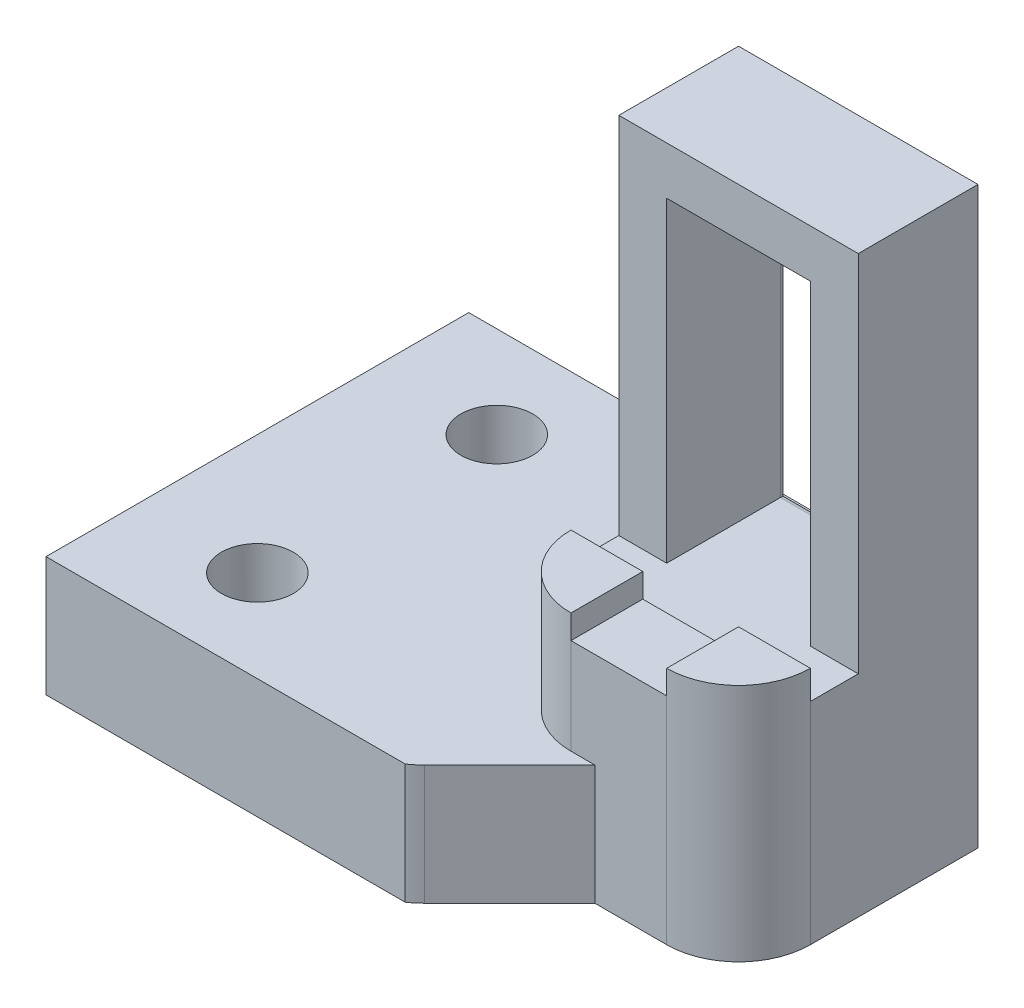
SolidWorks part; units mm, degrees
other "标注1"
sketch "草图8" plane through (-30, 24, -10.05) normal (-0.0333, 0.0376, -0.9987) x (-0.9561, 0.2897, 0.0428)
sketch "草图10" plane through (-30, 24, -10.05) normal (-0.0333, 0.0376, -0.9987) x (-0.9561, 0.2897, 0.0428)
sketch "草图23" plane through (-30, 24, -10) normal (-0.0333, 0.0376, -0.9987) x (-0.9561, 0.2897, 0.0428)
sketch "草图26" plane through (-30, 24, -10) normal (-0.0333, 0.0376, -0.9987) x (-0.9561, 0.2897, 0.0428)
sketch "草图30" plane through (-30, 24, -10) normal (-0.0333, 0.0376, -0.9987) x (-0.9561, 0.2897, 0.0428)
sketch "草图33" plane through (-30, 24, -10) normal (-0.0333, 0.0376, -0.9987) x (-0.9561, 0.2897, 0.0428)
sketch "草图41" plane through (-30, 24, -30) normal (-0.0333, 0.0376, -0.9987) x (-0.9561, 0.2897, 0.0428)
sketch "草图50" plane through (-62, 24, -30) normal (-0.0333, 0.0376, -0.9987) x (-0.9561, 0.2897, 0.0428)
sketch "草图56" plane through (-45, 24, -13.7305) normal (-0.0333, 0.0376, -0.9987) x (-0.9561, 0.2897, 0.0428)
other "标注2"
sketch "草图16" plane through (0, 24, 0) normal (0.8795, 0.3038, 0.3663) x (0.4513, -0.2881, -0.8446)
sketch "草图24" plane through (0, 24, 0) normal (0.8795, 0.3038, 0.3663) x (0.4513, -0.2881, -0.8446)
sketch "草图27" plane through (0, 24, 0) normal (0.8795, 0.3038, 0.3663) x (0.4513, -0.2881, -0.8446)
sketch "草图31" plane through (0, 24, 0) normal (0.8795, 0.3038, 0.3663) x (0.4513, -0.2881, -0.8446)
sketch "草图34" plane through (0, 24, 0) normal (0.8795, 0.3038, 0.3663) x (0.4513, -0.2881, -0.8446)
sketch "草图42" plane through (-10, 24, 10) normal (0.8795, 0.3038, 0.3663) x (0.4513, -0.2881, -0.8446)
sketch "草图51" plane through (-10, 24, 10) normal (0.8795, 0.3038, 0.3663) x (0.4513, -0.2881, -0.8446)
sketch "草图57" plane through (-10, 24, 3.9243) normal (0.8795, 0.3038, 0.3663) x (0.4513, -0.2881, -0.8446)
other "标注3"
sketch "草图17" plane through (0, 24, 0) normal (0.8795, 0.3038, 0.3663) x (0.4513, -0.2881, -0.8446)
sketch "草图25" plane through (0, 24, 0) normal (0.8795, 0.3038, 0.3663) x (0.4513, -0.2881, -0.8446)
sketch "草图28" plane through (0, 24, 0) normal (0.8795, 0.3038, 0.3663) x (0.4513, -0.2881, -0.8446)
sketch "草图32" plane through (0, 24, 0) normal (0.8795, 0.3038, 0.3663) x (0.4513, -0.2881, -0.8446)
sketch "草图35" plane through (0, 24, 0) normal (0.8795, 0.3038, 0.3663) x (0.4513, -0.2881, -0.8446)
sketch "草图43" plane through (-10, 24, 10) normal (0.8795, 0.3038, 0.3663) x (0.4513, -0.2881, -0.8446)
sketch "草图52" plane through (-10, 24, 10) normal (0.8795, 0.3038, 0.3663) x (0.4513, -0.2881, -0.8446)
sketch "草图58" plane through (-10, 24, 3.9243) normal (0.8795, 0.3038, 0.3663) x (0.4513, -0.2881, -0.8446)
other "标注4"
sketch "草图37" plane through (-30, 24, -10) normal (-0.8775, 0.4051, -0.2566) x (-0.3121, -0.0762, 0.947)
sketch "草图44" plane through (-30, 24, -30) normal (-0.8775, 0.4051, -0.2566) x (-0.3121, -0.0762, 0.947)
sketch "草图53" plane through (-62, 24, -30) normal (-0.8775, 0.4051, -0.2566) x (-0.3121, -0.0762, 0.947)
sketch "草图59" plane through (-45, 24, -13.7305) normal (-0.8775, 0.4051, -0.2566) x (-0.3121, -0.0762, 0.947)
ref_plane "前视基准面" through (0, 0, 0) normal (0, 0, 1) x (1, 0, 0)
ref_plane "上视基准面" through (0, 0, 0) normal (0, 1, 0) x (1, 0, 0)
ref_plane "右视基准面" through (0, 0, 0) normal (1, 0, 0) x (0, 0, -1)
other "Configuration Table"
sketch "草图1" plane through (0, 0, 0) normal (0, 1, 0) x (1, 0, 0)
  line L0 (-20, 0) -> (-20, -5)
  line L2 (0, 0) -> (0, 10)
  line L3 (0, 10) -> (-30, 10)
  line L4 (-30, 0) -> (-30, 10)
  line L5 (-20, -5) -> (-10, -5)
  line L6 (-10, -5) -> (-10, 0)
  line L7 (-30, 0) -> (-20, 0)
  line L8 (-10, 0) -> (0, 0)
  dimension "D1" = 10
  dimension "D2" = 30
  dimension "D3" = 10
  dimension "D4" = 10
  dimension "D5" = 5
  dimension "D6" = 5
extrude "凸台-拉伸1" add sketch "草图1" along normal blind 4
sketch "草图2" plane through (0, 4, 0) normal (0, 1, 0) x (1, 0, 0)
  line L7 (0, 10) -> (-30, 10) construction
  line L8 (-20, -5) -> (-10, -5)
  line L9 (-20, -5) -> (-20, 10)
  line L10 (-20, 10) -> (-10, 10)
  line L11 (-10, -5) -> (-10, 10)
extrude "凸台-拉伸2" add sketch "草图2" along normal blind 20
sketch "草图3" plane through (0, 4, 0) normal (0, 1, 0) x (1, 0, 0)
  line L2 (0, 10) -> (-10, 10) construction
  line L3 (0, 0) -> (0, 10) construction
  circle A1 centre (-5, 5) radius 1.45
  dimension "D3" = 5
  dimension "D4" = 5
  dimension "D6" = 2.9
extrude "切除-拉伸1" cut sketch "草图3" against normal blind 20
sketch "草图4" plane through (0, 0, -10) normal (0, 0, -1) x (-1, 0, 0)
  line L6 (10, 24) -> (10, 4) construction
  line L7 (12, 22) -> (18, 22)
  line L8 (12, 22) -> (12, 8.8)
  line L9 (12, 8.8) -> (18, 8.8)
  line L10 (18, 22) -> (18, 8.8)
  line L11 (10, 24) -> (20, 24) construction
  dimension "D1" = 6
  dimension "D2" = 13.2
  dimension "D3" = 2
  dimension "D4" = 2
extrude "切除-拉伸2" cut sketch "草图4" against normal blind 9.5
sketch "草图6" plane through (0, 0, -0.5) normal (0, 0, -1) x (-1, 0, 0)
  line L0 (15, 22) -> (15, 20.68) construction
  line L1 (18, 22) -> (12, 22) construction
  line L2 (15, 20.68) -> (15, 15.6) construction
  line L3 (15, 15.6) -> (15, 10.52) construction
  circle A0 centre (15, 20.68) radius 0.75
  circle A2 centre (15, 10.52) radius 0.75
  circle A3 centre (15, 15.6) radius 0.75
  dimension "D4" = 1.5
  dimension "D5" = 1.5
  dimension "D6" = 1.5
  dimension "D1" = 1.32
  dimension "D2" = 5.08
  dimension "D3" = 5.08
extrude "切除-拉伸4" cut sketch "草图6" against normal blind 3.5
sketch "草图7" plane through (0, 0, 5) normal (0, 0, 1) x (1, 0, 0)
  line L4 (-10, 24) -> (-20, 24)
  line L5 (-20, 24) -> (-20, 0)
  line L6 (-20, 0) -> (-10, 0)
  line L7 (-10, 0) -> (-10, 24)
  line L8 (-10, 24) -> (-20, 24)
  line L9 (-20, 24) -> (-20, 0)
  line L10 (-20, 0) -> (-10, 0)
  line L11 (-10, 0) -> (-10, 24)
  dimension "D1" = 0
extrude "切除-拉伸5" cut sketch "草图7" against normal blind 5
sketch "草图9" plane through (0, 0, -0.5) normal (0, 0, -1) x (-1, 0, 0)
  line L1 (13.5, 21.6) -> (16.5, 21.6)
  line L2 (13.5, 21.6) -> (13.5, 9.6)
  line L3 (13.5, 9.6) -> (16.5, 9.6)
  line L4 (16.5, 21.6) -> (16.5, 9.6)
  line L5 (13.5, 21.6) -> (16.5, 9.6) construction
  line L6 (13.5, 9.6) -> (16.5, 21.6) construction
  point P0 (15, 15.6)
  dimension "D1" = 3
  dimension "D2" = 12
extrude "切除-拉伸6" cut sketch "草图9" against normal blind 10
sketch "草图11" plane through (0, 0, -0.5) normal (0, 0, -1) x (-1, 0, 0)
  line L0 (18, 8.8) -> (18, 22) construction
  line L1 (16.5, 21.6) -> (18, 21.6)
  line L2 (16.5, 21.6) -> (16.5, 9.6)
  line L3 (16.5, 9.6) -> (18, 9.6)
  line L4 (18, 21.6) -> (18, 9.6)
  line L5 (12, 22) -> (12, 8.8) construction
  line L6 (13.5, 21.6) -> (12, 21.6)
  line L7 (13.5, 21.6) -> (13.5, 9.6)
  line L8 (13.5, 9.6) -> (12, 9.6)
  line L9 (12, 21.6) -> (12, 9.6)
extrude "切除-拉伸7" cut sketch "草图11" against normal blind 10
sketch "草图13" plane through (0, 24, 0) normal (0, 1, 0) x (1, 0, 0)
  line L0 (-10, 0) -> (-10, 10) construction
  line L1 (-20, 0) -> (-10, 0)
  line L2 (-20, 0) -> (-20, 5)
  line L3 (-20, 5) -> (-10, 5)
  line L4 (-10, 0) -> (-10, 5)
extrude "切除-拉伸8" cut sketch "草图13" against normal up to surface (20 mm away) up to face at (-5, 4, -3.55)
sketch "草图19" plane through (0, 4, 0) normal (0, 1, 0) x (1, 0, 0)
  line L1 (-20, 5) -> (-10, 5)
  line L2 (-20, 5) -> (-20, 2.6)
  line L3 (-20, 2.6) -> (-10, 2.6)
  line L4 (-10, 5) -> (-10, 2.6)
  dimension "D1" = 2.4
extrude "凸台-拉伸6" add sketch "草图19" along normal blind 4.8
sketch "草图20" plane through (0, 4, 0) normal (0, 1, 0) x (1, 0, 0)
  line L0 (-30, 0) -> (0, 0) construction
  line L1 (-20, 2.6) -> (-10, 2.6)
  line L2 (-20, 2.6) -> (-20, 0)
  line L3 (-20, 0) -> (-10, 0)
  line L4 (-10, 2.6) -> (-10, 0)
extrude "凸台-拉伸7" add sketch "草图20" along normal blind 6
fillet "圆角17" radius 0.25 4 edges at (-15, 8.8, -10) (-15, 22, -10) (-18, 15.4, -10) (-12, 15.4, -10)
sketch "草图21" plane through (0, 0, 0) normal (0, 0, 1) x (1, 0, 0)
  line L0 (-15, 10) -> (-15, 7.5151) construction
  line L1 (-20, 10) -> (-10, 10) construction
  line L2 (-13, 10) -> (-17, 10)
  line L3 (-17, 10) -> (-17, 9)
  line L4 (-17, 9) -> (-13, 9)
  line L5 (-13, 10) -> (-13, 9)
  point P9 (-15, 9)
  dimension "D1" = 2
  dimension "D2" = 1
extrude "切除-拉伸9" cut sketch "草图21" against normal blind 5.2
sketch "草图22" plane through (0, 0, -2.6) normal (0, 0, -1) x (-1, 0, 0)
  line L8 (17, 9) -> (13, 9)
  line L9 (13, 9) -> (13, 10)
  line L10 (13, 10) -> (10, 10)
  line L11 (10, 10) -> (10, 8.8)
  line L12 (10, 8.8) -> (20, 8.8)
  line L13 (20, 8.8) -> (20, 10)
  line L14 (20, 10) -> (17, 10)
  line L15 (17, 10) -> (17, 9)
  line L16 (17, 9) -> (13, 9)
  line L17 (13, 9) -> (13, 10)
  line L18 (13, 10) -> (10, 10)
  line L19 (10, 10) -> (10, 8.8)
  line L20 (10, 8.8) -> (20, 8.8)
  line L21 (20, 8.8) -> (20, 10)
  line L22 (20, 10) -> (17, 10)
  line L23 (17, 10) -> (17, 9)
  dimension "D1" = 0
extrude "凸台-拉伸8" add sketch "草图22" along normal blind 0.4
sketch "草图29" plane through (0, 4, 0) normal (0, 1, 0) x (1, 0, 0)
  line L0 (-30, 0) -> (-20, 0) construction
  line L1 (-20, 0) -> (-20, 10) construction
  line L2 (-20, 10) -> (-30, 10) construction
  line L3 (-30, 10) -> (-30, 0) construction
  line L4 (-10, 10) -> (-10, 0) construction
  line L5 (-10, 0) -> (0, 0) construction
  line L6 (0, 0) -> (0, 10) construction
  line L7 (0, 10) -> (-10, 10) construction
  line L8 (-30, 0) -> (-20, 0)
  line L9 (-20, 0) -> (-20, 10)
  line L10 (-20, 10) -> (-30, 10)
  line L11 (-30, 10) -> (-30, 0)
  line L12 (-10, 10) -> (-10, 0)
  line L13 (-10, 0) -> (0, 0)
  line L14 (0, 0) -> (0, 10)
  line L15 (0, 10) -> (-10, 10)
  circle A0 centre (-5, 5) radius 1.45 construction
  circle A2 centre (-5, 5) radius 1.45
extrude "凸台-拉伸9" add sketch "草图29" along normal blind 1
sketch "草图36" plane through (0, 5, 0) normal (0, 1, 0) x (1, 0, 0)
  line L4 (0, 10) -> (-10, 10)
  line L5 (-10, 10) -> (-10, 0)
  line L6 (-10, 0) -> (0, 0)
  line L7 (0, 0) -> (0, 10)
  line L8 (0, 10) -> (-10, 10)
  line L9 (-10, 10) -> (-10, 0)
  line L10 (-10, 0) -> (0, 0)
  line L11 (0, 0) -> (0, 10)
  dimension "D1" = 0
extrude "切除-拉伸10" cut sketch "草图36" against normal blind 10
sketch "草图38" plane through (0, 0, -10) normal (0, 0, -1) x (-1, 0, 0)
  line L0 (10, 0) -> (30, 0) construction
  line L1 (30, 5) -> (20, 5)
  line L2 (30, 5) -> (30, 0)
  line L3 (30, 0) -> (20, 0)
  line L4 (20, 5) -> (20, 0)
extrude "凸台-拉伸10" add sketch "草图38" along normal blind 20
sketch "草图39" plane through (0, 0, 0) normal (0, 0, 1) x (1, 0, 0)
  line L1 (-20, 5) -> (-30, 5)
  line L2 (-20, 5) -> (-20, 0)
  line L3 (-20, 0) -> (-30, 0)
  line L4 (-30, 5) -> (-30, 0)
extrude "凸台-拉伸11" add sketch "草图39" along normal blind 10
sketch "草图40" plane through (0, 5, 0) normal (0, 1, 0) x (1, 0, 0)
  line L0 (-25, 30) -> (-25, 25) construction
  line L1 (-30, 30) -> (-20, 30) construction
  line L2 (-25, 25) -> (-25, -5) construction
  circle A0 centre (-25, 25) radius 1.5
  circle A1 centre (-25, -5) radius 1.5
  dimension "D3" = 3
  dimension "D4" = 3
  dimension "D1" = 5
  dimension "D2" = 30
extrude "切除-拉伸11" cut sketch "草图40" against normal blind 15
chamfer "倒角1" distance 4 angle 45 2 edges at (-20, 2.5, 0) (-20, 2.5, -10)
sketch "草图46" plane through (-30, 0, 0) normal (-1, 0, 0) x (0, 0, 1)
  line L4 (-30, 0) -> (10, 0)
  line L5 (10, 0) -> (10, 5)
  line L6 (10, 5) -> (-30, 5)
  line L7 (-30, 5) -> (-30, 0)
  line L8 (-30, 0) -> (10, 0)
  line L9 (10, 0) -> (10, 5)
  line L10 (10, 5) -> (-30, 5)
  line L11 (-30, 5) -> (-30, 0)
  dimension "D1" = 0
extrude "凸台-拉伸12" add sketch "草图46" along normal blind 32
sketch "草图47" plane through (0, 5, 0) normal (0, 1, 0) x (1, 0, 0)
  line L0 (-41, 30) -> (-41, -12.535) construction
  line L1 (-62, 30) -> (-20, 30) construction
  circle A0 centre (-25, -5) radius 1.5 construction
  circle A1 centre (-25, 25) radius 1.5 construction
  circle A2 centre (-25, -5) radius 1.5
  circle A3 centre (-25, 25) radius 1.5
  circle A4 centre (-57, 25) radius 1.5
  circle A5 centre (-57, -5) radius 1.5
extrude "切除-拉伸12" cut sketch "草图47" against normal blind 10
sketch "草图48" plane through (0, 5, 0) normal (0, 1, 0) x (1, 0, 0)
  line L1 (-20, 30) -> (-44, 30)
  line L2 (-20, 30) -> (-20, 14)
  line L3 (-20, 14) -> (-44, 14)
  line L4 (-44, 30) -> (-44, 14)
  line L5 (-20, -10) -> (-44, -10)
  line L6 (-20, -10) -> (-20, -3.9243)
  line L7 (-20, -3.9243) -> (-44, -3.9243)
  line L8 (-44, -10) -> (-44, -3.9243)
  dimension "D1" = 24
  dimension "D2" = 24
extrude "切除-拉伸13" cut sketch "草图48" against normal blind 10
sketch "草图49" plane through (0, 5, 0) normal (0, 1, 0) x (1, 0, 0)
  line L0 (-26.0454, -3.9243) -> (-23.9546, -3.9243)
  arc A0 (-23.9546, -3.9243) -> (-26.0454, -3.9243) centre (-25, -5) ccw construction
  arc A1 (-23.9546, -3.9243) -> (-26.0454, -3.9243) centre (-25, -5) ccw
extrude "凸台-拉伸13" add sketch "草图49" against normal up to surface (5 mm away) up to face at (-57, 0, 6.5)
chamfer "倒角2" distance 6 angle 45 2 edges at (-44, 2.5, 3.9243) (-44, 2.5, -14)
fillet "圆角18" radius 3 8 edges at (-20, 7.5, 0) (-10, 5, 0) (-20, 2.5, 4) (-20, 2.5, -14) (-44, 2.5, 10) (-62, 2.5, 10) (-62, 2.5, -30) (-44, 2.5, -30)
sketch "草图54" plane through (0, 5, 0) normal (0, 1, 0) x (1, 0, 0)
  line L2 (-20, 3) -> (-20, 37.8189)
  line L3 (-20, 37.8189) -> (-71.4005, 37.8189)
  line L4 (-71.4005, 3) -> (-71.4005, 37.8189)
  line L6 (-20, 3) -> (-20, -21.7642)
  line L7 (-20, -21.7642) -> (-71.4005, -21.7642)
  line L8 (-71.4005, 3) -> (-71.4005, -21.7642)
extrude "切除-拉伸14" cut sketch "草图54" against normal blind 10
sketch "草图55" plane through (-20, 0, 0) normal (-1, 0, 0) x (0, 0, 1)
  line L1 (-13.7305, 5) -> (3.9243, 5)
  line L2 (-13.7305, 5) -> (-13.7305, 0)
  line L3 (-13.7305, 0) -> (3.9243, 0)
  line L4 (3.9243, 5) -> (3.9243, 0)
extrude "凸台-拉伸14" add sketch "草图55" along normal blind 25
sketch "草图60" plane through (-45, 0, 0) normal (-1, 0, 0) x (0, 0, 1)
  line L4 (-13.7305, 5) -> (-13.7305, 0)
  line L5 (-13.7305, 0) -> (3.9243, 0)
  line L6 (3.9243, 0) -> (3.9243, 5)
  line L7 (3.9243, 5) -> (-13.7305, 5)
  line L8 (-13.7305, 5) -> (-13.7305, 0)
  line L9 (-13.7305, 0) -> (3.9243, 0)
  line L10 (3.9243, 0) -> (3.9243, 5)
  line L11 (3.9243, 5) -> (-13.7305, 5)
  dimension "D1" = 0
extrude "切除-拉伸15" cut sketch "草图60" against normal blind 10
sketch "草图61" plane through (0, 5, 0) normal (0, 1, 0) x (1, 0, 0)
  line L0 (-30, 13.7305) -> (-30, 9.9031) construction
  line L2 (-35, 4.9031) -> (-28.4747, 4.9031) construction
  line L3 (-35, -3.9243) -> (-35, 13.7305) construction
  circle A0 centre (-30, 9.9031) radius 1.5
  circle A1 centre (-30, -0.0969) radius 1.5
  dimension "D2" = 3
  dimension "D1" = 5
  dimension "D3" = 5
extrude "切除-拉伸16" cut sketch "草图61" against normal blind 10
sketch "草图66" plane through (0, 5, 0) normal (0, 1, 0) x (1, 0, 0)
  line L1 (-20, 10) -> (-15.1304, 10)
  line L2 (-20, 10) -> (-20, 14.3389)
  line L3 (-20, 14.3389) -> (-15.1304, 14.3389)
  line L4 (-15.1304, 10) -> (-15.1304, 14.3389)
extrude "切除-拉伸17" cut sketch "草图66" against normal blind 14
